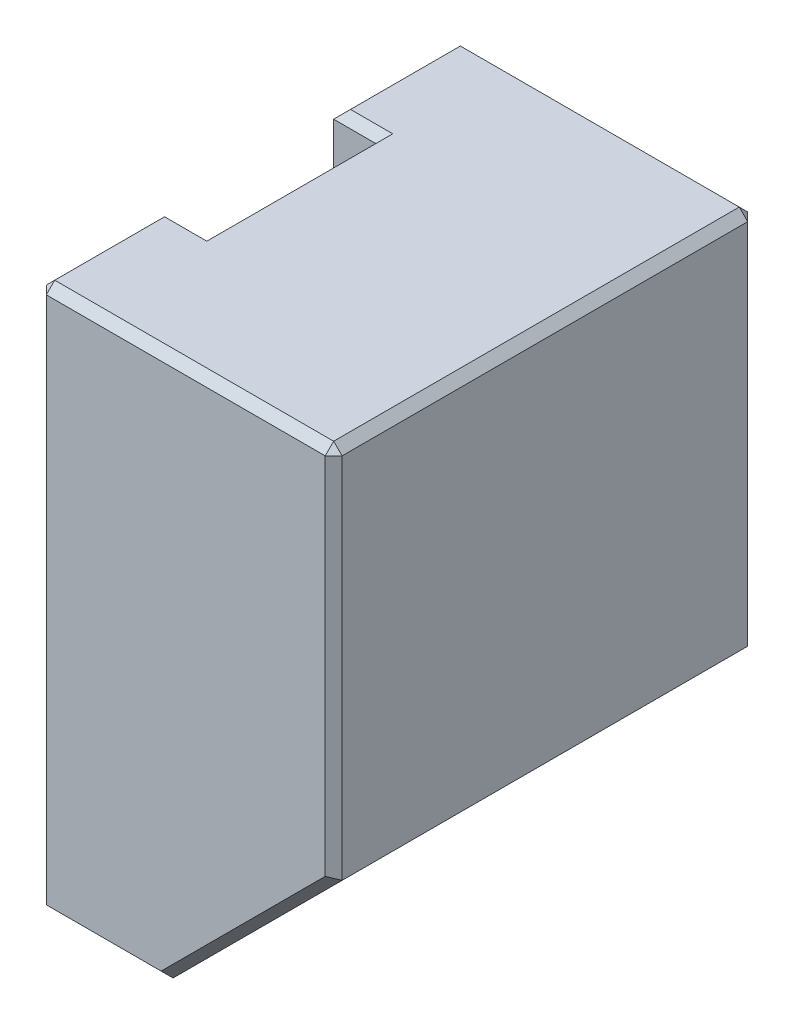
SolidWorks part; units mm, degrees
material "K110"
ref_plane "Front Plane" through (0, 0, 0) normal (0, 0, 1) x (1, 0, 0)
ref_plane "Top Plane" through (0, 0, 0) normal (0, 1, 0) x (1, 0, 0)
ref_plane "Right Plane" through (0, 0, 0) normal (1, 0, 0) x (0, 0, -1)
sketch "Sketch1" plane through (0, 0, 0) normal (0, 1, 0) x (1, 0, 0)
  line L1 (-17.5, -24.995) -> (17.5, -24.995)
  line L2 (-17.5, -24.995) -> (-17.5, 24.995)
  line L3 (-17.5, 24.995) -> (17.5, 24.995)
  line L4 (17.5, -24.995) -> (17.5, 24.995)
  line L5 (-17.5, -24.995) -> (17.5, 24.995) construction
  line L6 (-17.5, 24.995) -> (17.5, -24.995) construction
  point P0 (0, 0)
  dimension "D1" = 49.99
  dimension "D2" = 35
extrude "Boss-Extrude1" add sketch "Sketch1" against normal blind 64.5
sketch "Sketch2" plane through (0, 0, 24.995) normal (0, 0, 1) x (1, 0, 0)
  line L0 (-2.5, -64.5) -> (17.5, -44.5)
  line L1 (-17.5, -64.5) -> (17.5, -64.5) construction
  line L2 (17.5, -64.5) -> (17.5, 0) construction
  line L3 (17.5, -44.5) -> (17.5, -64.5)
  line L4 (17.5, -64.5) -> (-2.5, -64.5)
  dimension "D1" = 20
  dimension "D2" = 45
extrude "Cut-Extrude1" cut sketch "Sketch2" against normal up to next
sketch "Sketch3" plane through (-17.5, 0, 0) normal (-1, 0, 0) x (0, 0, 1)
  line L0 (-24.995, -64.5) -> (24.995, -64.5) construction
  line L1 (-7, -64.5) -> (7, -64.5)
  line L2 (-7, -64.5) -> (-7, -44.5)
  line L3 (-7, -44.5) -> (7, -44.5)
  line L4 (7, -64.5) -> (7, -44.5)
  line L5 (-24.995, -44.5) -> (24.995, -44.5) construction
  point P8 (0, -44.5)
  dimension "D1" = 14
  dimension "D2" = 20
extrude "Cut-Extrude2" cut sketch "Sketch3" against normal up to next
fillet "Fillet1" 2 edges at (0, -44.5, -7) (0, -44.5, 7) type full round first side face at (-5, -54.5, -7) second side face at (-5, -54.5, 7) middle face at (0, -44.5, 0)
sketch "Sketch4" plane through (0, 0, 0) normal (0, 1, 0) x (1, 0, 0)
  line L0 (-17.5, 0) -> (17.5, 0) construction
  line L1 (-17.5, 24.995) -> (-17.5, -24.995) construction
  line L2 (17.5, -24.995) -> (17.5, 24.995) construction
  line L4 (-17.5, -10) -> (-12.5, -10)
  line L5 (-17.5, -10) -> (-17.5, 10)
  line L6 (-17.5, 10) -> (-12.5, 10)
  line L7 (-12.5, -10) -> (-12.5, 10)
  dimension "D1" = 5
  dimension "D2" = 20
extrude "Cut-Extrude3" cut sketch "Sketch4" against normal blind 43
sketch "Sketch5" plane through (-17.5, 0, 0) normal (-1, 0, 0) x (0, 0, 1)
  line L0 (-10, -43) -> (-10, 0) construction
  line L1 (-15, -43) -> (15, -43)
  line L2 (-15, -43) -> (-15, -38)
  line L3 (-15, -38) -> (15, -38)
  line L4 (15, -43) -> (15, -38)
  line L5 (-10, -43) -> (10, -43) construction
  line L6 (10, -43) -> (10, 0) construction
  dimension "D1" = 5
  dimension "D2" = 5
  dimension "D3" = 5
extrude "Cut-Extrude4" cut sketch "Sketch5" against normal up to surface (5 mm away) up to face at (-12.5, -21.5, 0)
fillet "Fillet5" 2 edges at (-15, -43, -15) (-15, -38, -15) type full round first side face at (-15, -43, 0) second side face at (-15, -38, -12.5) middle face at (-15, -40.5, -15)
fillet "Fillet6" 2 edges at (-15, -43, 15) (-15, -38, 15) type full round first side face at (-15, -43, 1.25) second side face at (-15, -38, 12.5) middle face at (-15, -40.5, 15)
chamfer "Chamfer1" distance 1 angle 45 16 edges at (17.5, 0, 0) (17.5, -22.25, -24.995) (0, 0, -24.995) (7.5, -54.5, -24.995) (-10, -64.5, -24.995) (-17.5, -32.25, -24.995) (-17.5, 0, -17.4975) (-15, 0, -10) (-12.5, 0, 0) (-15, 0, 10) (-17.5, 0, 17.4975) (-10, -64.5, 24.995) (-17.5, -32.25, 24.995) (0, 0, 24.995) (17.5, -22.25, 24.995) (7.5, -54.5, 24.995)
sketch "Sketch6" [suppressed] plane through (0, 0, 24.995) normal (0, 0, 1) x (1, 0, 0)
  line L0 (-16.5, 0) -> (16.5, 0) construction
  line L1 (-17.5, -63.5) -> (-17.5, -1) construction
  circle A0 centre (-10, -15) radius 2.5
  dimension "D1" = 5
  dimension "D2" = 15
  dimension "D3" = 7.5
extrude "Cut-Extrude5" [suppressed] cut sketch "Sketch6" against normal blind 3
pattern_linear "LPattern1" [suppressed] count 3 spacing 10 count 5 spacing 10 of bodies 106
sketch "Sketch9" [suppressed] plane through (17.5, 0, 0) normal (1, 0, 0) x (0, 0, -1)
  line L0 (-24.995, -44.0858) -> (-24.995, -1) construction
  line L1 (-23.995, 0) -> (23.995, 0) construction
  circle A0 centre (-18.745, -15) radius 2.5
  dimension "D1" = 5
  dimension "D2" = 6.25
  dimension "D3" = 15
extrude "Cut-Extrude20" [suppressed] cut sketch "Sketch9" against normal blind 3
pattern_linear "LPattern2" [suppressed] count 4 spacing 7.5 count 6 spacing 7.5 of bodies 110
sketch "Sketch10" [suppressed] plane through (-17.5, 0, 0) normal (-1, 0, 0) x (0, 0, 1)
  line L0 (-11, -1) -> (-23.995, -1) construction
  line L2 (-23.995, 0) -> (-11, 0) construction
  circle A0 centre (-17.4975, -15) radius 2.5
  point P7 (-17.4975, -1)
  dimension "D1" = 5
  dimension "D2" = 15
extrude "Cut-Extrude21" [suppressed] cut sketch "Sketch10" against normal blind 3
pattern_linear "LPattern3" [suppressed] count 7 spacing 7.5 count 2 spacing 35 of bodies 112
sketch "Sketch11" [suppressed] plane through (31, -31, 0) normal (0.7071, -0.7071, 0) x (0, 0, -1)
  line L0 (-24.995, -46.9619) -> (-24.995, -19.5061) construction
  line L2 (0, -19.0919) -> (-23.995, -19.0919) construction
  circle A0 centre (-18.745, -26.5919) radius 2.5
  dimension "D1" = 6.25
  dimension "D2" = 5
  dimension "D5" = 7.5
extrude "Cut-Extrude23" [suppressed] cut sketch "Sketch11" against normal blind 3
pattern_linear "LPattern5" [suppressed] count 6 spacing 7.5 count 3 spacing 7.5 of bodies 115
sketch "Sketch18" [suppressed] plane through (0, 0, -25) normal (0, 0, -1) x (-1, 0, 0)
  circle A0 centre (10, -15) radius 2.5
extrude "Cut-Extrude25" [suppressed] cut sketch "Sketch18" against normal blind 3
pattern_linear "LPattern7" [suppressed] count 3 spacing 10 count 5 spacing 10 of bodies 121
ref_plane "Plane1" through (31, -31, 0) normal (0.7071, -0.7071, 0) x (-0.7071, -0.7071, 0)
sketch "Sketch19" plane through (31, -31, 0) normal (0.7071, -0.7071, 0) x (0, 0, -1)
  line L0 (-24.995, -33.234) -> (24.995, -33.234)
  line L1 (-24.995, -19.0919) -> (-24.995, -47.3762) construction
  line L2 (24.995, -19.0919) -> (24.995, -47.3762) construction
  line L3 (0, -19.0919) -> (0, -33.234)
